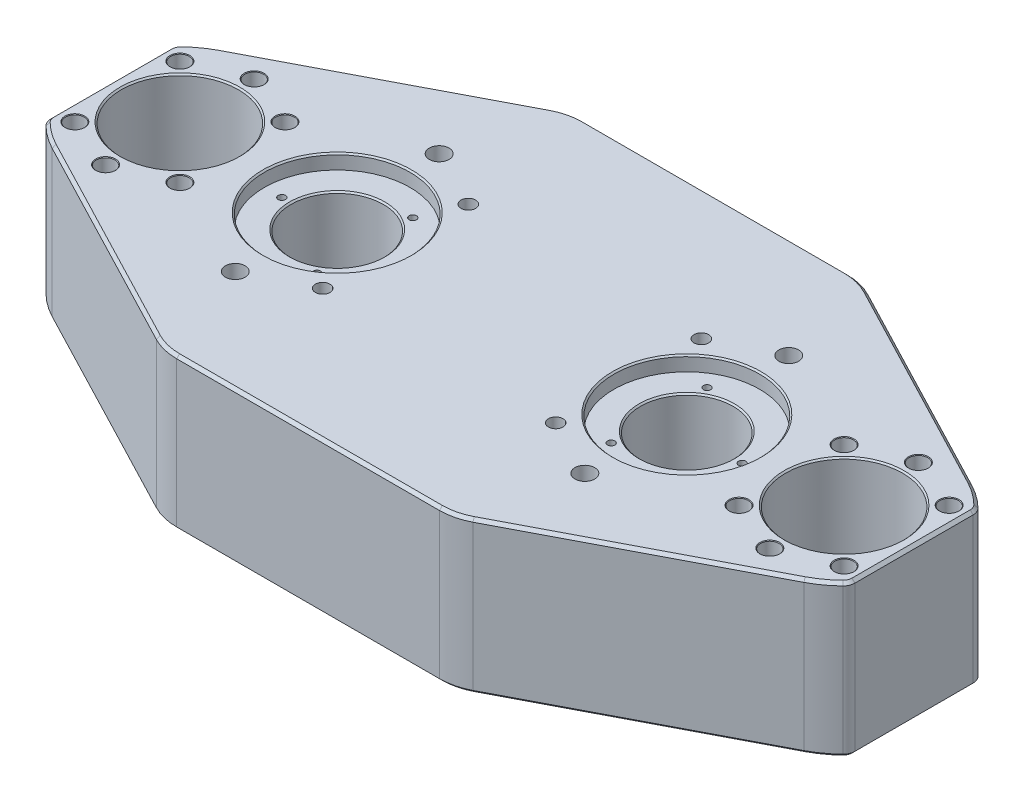
SolidWorks part; units mm, degrees
material "6061-T6 Aluminum"
ref_plane "Front Plane" through (0, 0, 0) normal (0, 0, 1) x (1, 0, 0)
ref_plane "Top Plane" through (0, 0, 0) normal (0, 1, 0) x (1, 0, 0)
ref_plane "Right Plane" through (0, 0, 0) normal (1, 0, 0) x (0, 0, -1)
sketch "Sketch1" plane through (0, 0, 0) normal (0, 1, 0) x (1, 0, 0)
  line L0 (114, 0) -> (0, 0) construction
  line L1 (0, 0) -> (-114, 0) construction
  line L2 (-60, 0) -> (0, 0) construction
  line L3 (0, 0) -> (60, 0) construction
  line L18 (0, 70) -> (0, 0) construction
  line L19 (0, 0) -> (0, -70) construction
  line L20 (-129.0194, 28.8213) -> (-54.3441, 67.7362)
  line L21 (-45.1014, 70) -> (45.1014, 70)
  line L22 (54.3441, 67.7362) -> (129.0194, 28.8213)
  line L23 (-129.0194, -28.8213) -> (-54.3441, -67.7362)
  line L24 (-45.1014, -70) -> (45.1014, -70)
  line L25 (54.3441, -67.7362) -> (129.0194, -28.8213)
  line L26 (-138, 20.3039) -> (-138, -20.3039)
  line L27 (138, 20.3039) -> (138, -20.3039)
  line L28 (-138, 0) -> (-114, 0) construction
  line L29 (114, 0) -> (138, 0) construction
  circle A0 centre (-114, 0) radius 20.1
  circle A1 centre (114, 0) radius 20.1
  circle A2 centre (-60, 0) radius 15.875
  circle A3 centre (60, 0) radius 15.875
  arc A6 (-54.3441, -67.7362) -> (-45.1014, -70) centre (-45.1014, -50) ccw
  arc A7 (45.1014, -70) -> (54.3441, -67.7362) centre (45.1014, -50) ccw
  arc A8 (-129.0194, 28.8213) -> (-136.807, 23.1536) centre (-114, 0) ccw
  arc A9 (129.0194, -28.8213) -> (136.807, -23.1536) centre (114, 0) ccw
  arc A10 (45.1014, 70) -> (54.3441, 67.7362) centre (45.1014, 50) cw
  arc A11 (-54.3441, 67.7362) -> (-45.1014, 70) centre (-45.1014, 50) cw
  arc A12 (-136.807, -23.1536) -> (-129.0194, -28.8213) centre (-114, 0) ccw
  arc A13 (136.807, 23.1536) -> (129.0194, 28.8213) centre (114, 0) ccw
  arc A14 (136.807, -23.1536) -> (138, -20.3039) centre (134, -20.3039) ccw
  arc A15 (136.807, 23.1536) -> (138, 20.3039) centre (134, 20.3039) cw
  arc A16 (-136.807, -23.1536) -> (-138, -20.3039) centre (-134, -20.3039) cw
  arc A17 (-136.807, 23.1536) -> (-138, 20.3039) centre (-134, 20.3039) ccw
  point P30 (-50, -70)
  point P36 (50, 70)
  point P39 (-50, 70)
  dimension "D1" = 40.2
  dimension "D3" = 120
  dimension "D7" = 31.75
  dimension "D8" = 20
  dimension "D6" = 32.5
  dimension "D9" = 276
  dimension "D10" = 4
  dimension "D11" = 32.5
  dimension "D2" = 228
  dimension "D4" = 140
  dimension "D5" = 100
extrude "Boss-Extrude1" add sketch "Sketch1" along normal mid plane 52
sketch "Sketch7" plane through (0, -26, 0) normal (0, -1, 0) x (1, 0, 0)
  circle A0 centre (95.9688, 18.0312) radius 3.3 construction
  circle A1 centre (114, 25.5) radius 3.3 construction
  circle A2 centre (132.0312, 18.0312) radius 3.3 construction
  circle A3 centre (132.0312, -18.0312) radius 3.3 construction
  circle A4 centre (114, -25.5) radius 3.3 construction
  circle A5 centre (95.9688, -18.0312) radius 3.3 construction
  circle A6 centre (95.9688, 18.0312) radius 3.3
  circle A7 centre (114, 25.5) radius 3.3
  circle A8 centre (132.0312, 18.0312) radius 3.3
  circle A9 centre (132.0312, -18.0312) radius 3.3
  circle A10 centre (114, -25.5) radius 3.3
  circle A11 centre (95.9688, -18.0312) radius 3.3
hole_wizard "M6 Clearance Hole1" positions "Sketch8" profile "Sketch9" hole size "M6" standard "ANSI Metric" end condition through all
sketch "Sketch8" plane through (0, -26, 0) normal (0, -1, 0) x (-1, 0, 0)
  point P0 (-95.9688, -18.0312)
  point P3 (-114, -25.5)
  point P6 (-132.0312, -18.0312)
  point P9 (-132.0312, 18.0312)
  point P12 (-114, 25.5)
  point P15 (-95.9688, 18.0312)
sketch "Sketch9" plane through (95.9688, -26, 18.0312) normal (1, 0, 0) x (0, 0, -1)
  line L0 (0, 0) -> (0, 52)
  line L1 (0, 52) -> (3.2, 52)
  line L2 (3.2, 52) -> (3.2, 0)
  line L5 (3.2, 0) -> (0, 0)
  line L11 (0, -6.35) -> (0, 107.95) construction
  dimension "Thru Hole Dia." = 6.4
  dimension "Thru Hole Depth" = 52
mirror "Mirror5" about plane through (0, 0, 0) normal (1, 0, 0) of "M6 Clearance Hole1"
chamfer "Chamfer2" distance 0.5 angle 45 4 edges at (114, 26, 20.1) (114, -26, 20.1) (-114, -26, 20.1) (-114, 26, 20.1)
chamfer "Chamfer3" [suppressed] distance 1 angle 45
chamfer "Chamfer5" distance 1 angle 45 40 edges at (91.6818, -26, -48.2787) (-91.6818, -26, -48.2787) (49.8594, -26, -69.4258) (-49.8594, -26, -69.4258) (0, -26, -70) (-133.1243, -26, -26.2776) (133.1243, -26, 26.2776) (-91.6818, -26, 48.2787) (91.6818, -26, 48.2787) (-49.8594, -26, 69.4258) (49.8594, -26, 69.4258) (0, -26, 70) (91.6818, 26, -48.2787) (-91.6818, 26, -48.2787) (49.8594, 26, -69.4258) (-49.8594, 26, -69.4258) (0, 26, -70) (-133.1243, 26, -26.2776) (133.1243, 26, 26.2776) (-91.6818, 26, 48.2787) (91.6818, 26, 48.2787) (-49.8594, 26, 69.4258) (49.8594, 26, 69.4258) (0, 26, 70) (133.1243, -26, -26.2776) (-133.1243, -26, 26.2776) (133.1243, 26, -26.2776) (-133.1243, 26, 26.2776) (-137.6897, -26, -21.8486) (137.6897, -26, -21.8486) (-138, -26, 0) (138, -26, 0) (-137.6897, -26, 21.8486) (137.6897, -26, 21.8486) (-137.6897, 26, -21.8486) (137.6897, 26, -21.8486) (-138, 26, 0) (138, 26, 0) (-137.6897, 26, 21.8486) (137.6897, 26, 21.8486)
chamfer "Chamfer6" distance 0.5 angle 45 4 edges at (60, -26, 15.875) (60, 26, 15.875) (-60, -26, 15.875) (-60, 26, 15.875)
sketch "Sketch10" plane through (0, 26, 0) normal (0, 1, 0) x (1, 0, 0)
  line L0 (50.5, -16.4545) -> (50.5, 16.4545) construction
  line L1 (50.5, 16.4545) -> (79, 0) construction
  line L2 (79, 0) -> (50.5, -16.4545) construction
  circle A3 centre (50.5, -16.4545) radius 1.7
  circle A4 centre (50.5, 16.4545) radius 1.7
  circle A5 centre (79, 0) radius 1.7
  circle A6 centre (60, 0) radius 19 construction
  dimension "D1" = 38
hole_wizard "M3x0.5 Tapped Hole1" positions "Sketch11" profile "Sketch13" tap size "M3x0.5" standard "ANSI Metric"
sketch "Sketch11" plane through (0, 26, 0) normal (0, 1, 0) x (1, 0, 0)
  point P0 (79, 0)
  point P3 (50.5, -16.4545)
  point P6 (50.5, 16.4545)
sketch "Sketch13" plane through (79, 26, 0) normal (1, 0, 0) x (0, 0, 1)
  line L0 (0, 0) -> (0, 12.7511)
  line L1 (0, 12.7511) -> (1.25, 12)
  line L2 (1.25, 12) -> (1.25, 0)
  line L5 (1.25, 0) -> (0, 0)
  line L10 (0, 12.7511) -> (-1.25, 12) construction
  line L11 (0, -6.35) -> (0, 107.95) construction
  dimension "Tap Drill Dia." = 2.5
  dimension "Tap Drill Depth" = 12
  dimension "Drill Angle" = 118
cosmetic thread "Hole Thread9" parameters "D1"=10, "D2"=3
cosmetic thread "Hole Thread13" parameters "D1"=10, "D2"=3
cosmetic thread "Hole Thread14" parameters "D1"=10, "D2"=3
mirror "Mirror6" about plane through (0, 0, 0) normal (1, 0, 0) of "M3x0.5 Tapped Hole1"
mirror "Mirror7" about plane through (0, 0, 0) normal (0, 1, 0) of "Mirror6"
sketch "Sketch14" plane through (0, -26, 0) normal (0, -1, 0) x (1, 0, 0)
  line L0 (-60, 0) -> (-60, -35) construction
  circle A1 centre (-60, -35) radius 3.25
  dimension "D1" = 35
chamfer "Chamfer9" distance 0.2 angle 45 24 edges at (-132.0312, -26, -21.2312) (-132.0312, 26, -21.2312) (-114, -26, -28.7) (-114, 26, -28.7) (-95.9688, -26, -21.2312) (-95.9688, 26, -21.2312) (-95.9688, -26, 14.8312) (-95.9688, 26, 14.8312) (-114, -26, 22.3) (-114, 26, 22.3) (-132.0312, -26, 14.8312) (-132.0312, 26, 14.8312) (132.0312, -26, 14.8312) (132.0312, 26, 14.8312) (114, -26, 22.3) (114, 26, 22.3) (95.9688, -26, 14.8312) (95.9688, 26, 14.8312) (95.9688, -26, -21.2312) (95.9688, 26, -21.2312) (132.0312, -26, -21.2312) (132.0312, 26, -21.2312) (114, -26, -28.7) (114, 26, -28.7)
sketch "Sketch15" plane through (0, -26, 0) normal (0, -1, 0) x (1, 0, 0)
  circle A1 centre (-60, -35) radius 3.05
  point P0 (-60, -35)
hole_wizard "M8x1.25 Tapped Hole1" positions "Sketch15" profile "Sketch16" tap size "M8x1.25" standard "ANSI Metric" end condition through all
cosmetic thread "Hole Thread15" parameters "D2"=8
sketch "Sketch16" plane through (-60, -26, -35) normal (1, 0, 0) x (0, 0, -1)
  line L0 (0, 0) -> (0, 52)
  line L1 (0, 52) -> (3.4, 52)
  line L2 (3.4, 52) -> (3.4, 0)
  line L5 (3.4, 0) -> (0, 0)
  line L11 (0, -6.35) -> (0, 107.95) construction
  dimension "Thru Tap Drill Dia." = 6.8
  dimension "Thru Tap Drill Depth" = 52
mirror "Mirror8" about plane through (0, 0, 0) normal (0, 0, 1) of "M8x1.25 Tapped Hole1"
mirror "Mirror9" about plane through (0, 0, 0) normal (1, 0, 0) of "Mirror8"
sketch "Sketch17" plane through (0, 26, 0) normal (0, 1, 0) x (1, 0, 0)
  circle A0 centre (60, 0) radius 25
  circle A1 centre (-60, 0) radius 25
  dimension "D1" = 50
  dimension "D2" = 50
extrude "Cut-Extrude1" cut sketch "Sketch17" against normal blind 5
mirror "Mirror10" about plane through (0, 0, 0) normal (0, 1, 0) of "Cut-Extrude1"
chamfer "Chamfer10" distance 0.5 angle 45 8 edges at (60, -21, -15.875) (60, 21, 15.875) (-60, -21, -15.875) (-60, 21, 15.875) (60, -26, 25) (-60, -26, 25) (60, 26, 25) (-60, 26, 25)
sketch "Sketch18" plane through (0, -26, 0) normal (0, -1, 0) x (1, 0, 0)
  line L1 (-40, -25) -> (40, -25) construction
  line L2 (-40, -25) -> (-40, 25) construction
  line L3 (-40, 25) -> (40, 25) construction
  line L4 (40, -25) -> (40, 25) construction
  line L5 (-40, -25) -> (40, 25) construction
  line L6 (-40, 25) -> (40, -25) construction
  point P0 (0, 0)
  dimension "D1" = 50
  dimension "D2" = 80
sketch "Sketch19" plane through (0, -26, 0) normal (0, -1, 0) x (-1, 0, 0)
  point P0 (40, 25)
  point P3 (40, -25)
  point P6 (-40, 25)
  point P9 (-40, -25)
hole_wizard "M6x1.0 Tapped Hole1" positions "Sketch19" profile "Sketch20" tap size "M6x1.0" standard "ANSI Metric"
sketch "Sketch20" plane through (-40, -26, -25) normal (1, 0, 0) x (0, 0, -1)
  line L0 (0, 0) -> (0, 16.5022)
  line L1 (0, 16.5022) -> (2.5, 15)
  line L2 (2.5, 15) -> (2.5, 0)
  line L5 (2.5, 0) -> (0, 0)
  line L10 (0, 16.5022) -> (-2.5, 15) construction
  line L11 (0, -6.35) -> (0, 107.95) construction
  dimension "Tap Drill Dia." = 5
  dimension "Tap Drill Depth" = 15
  dimension "Drill Angle" = 118
cosmetic thread "Hole Thread16" parameters "D1"=12, "D2"=6
cosmetic thread "Hole Thread17" parameters "D1"=12, "D2"=6
cosmetic thread "Hole Thread18" parameters "D1"=12, "D2"=6
cosmetic thread "Hole Thread19" parameters "D1"=12, "D2"=6
mirror "Mirror11" about plane through (0, 0, 0) normal (0, 1, 0) of "M6x1.0 Tapped Hole1"
